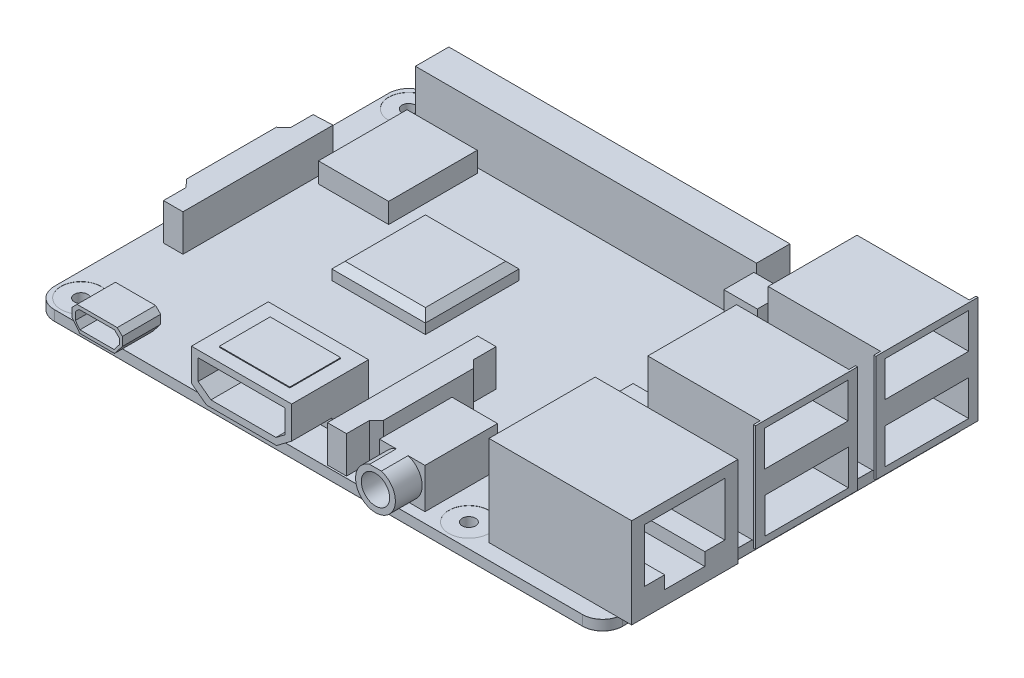
SolidWorks part; units mm, degrees
material "custom glass fiber"
ref_plane "Front Plane" through (0, 0, 0) normal (0, 0, 1) x (1, 0, 0)
ref_plane "Top Plane" through (0, 0, 0) normal (0, 1, 0) x (1, 0, 0)
ref_plane "Right Plane" through (0, 0, 0) normal (1, 0, 0) x (0, 0, -1)
sketch "Sketch1" plane through (0, 0, 0) normal (0, 1, 0) x (1, 0, 0)
  line L0 (32.5, 56) -> (32.5, 0) construction
  line L1 (3, 0) -> (82, 0)
  line L2 (0, 3) -> (0, 53)
  line L3 (3, 56) -> (82, 56)
  line L4 (85, 3) -> (85, 53)
  arc A0 (3, 0) -> (0, 3) centre (3, 3) cw
  arc A1 (82, 0) -> (85, 3) centre (82, 3) ccw
  arc A2 (82, 56) -> (85, 53) centre (82, 53) cw
  arc A3 (0, 53) -> (3, 56) centre (3, 53) cw
  circle A4 centre (3.5, 52.5) radius 1
  circle A5 centre (3.5, 3.5) radius 1
  circle A6 centre (61.5, 3.5) radius 1
  circle A7 centre (61.5, 52.5) radius 1
  point P7 (0, 0)
  point P12 (85, 56)
  point P15 (0, 56)
  dimension "D3" = 3
  dimension "D4" = 2
  dimension "D1" = 56
  dimension "D2" = 85
  dimension "D5" = 49
  dimension "D6" = 3.5
  dimension "D7" = 3.5
  dimension "D8" = 58
extrude "Boss-Extrude1" add sketch "Sketch1" along normal blind 1.4732
sketch "Sketch2" plane through (0, 1.4732, 0) normal (0, 1, 0) x (1, 0, 0)
  line L0 (3, 56) -> (82, 56)
  line L1 (85, 3) -> (85, 53)
  line L2 (85, 3) -> (85, 53) construction
  line L3 (82, 0) -> (3, 0)
  line L4 (0, 3) -> (0, 53)
  line L5 (3.5, 3.5) -> (61.5, 3.5) construction
  line L6 (32.5, 3.5) -> (32.5, 56) construction
  arc A0 (82, 56) -> (85, 53) centre (82, 53) cw
  arc A1 (82, 0) -> (85, 3) centre (82, 3) ccw construction
  arc A2 (85, 3) -> (82, 0) centre (82, 3) cw
  arc A3 (3, 0) -> (0, 3) centre (3, 3) cw
  arc A4 (0, 53) -> (3, 56) centre (3, 53) cw
  circle A5 centre (3.5, 52.5) radius 3
  circle A6 centre (3.5, 3.5) radius 3
  circle A7 centre (61.5, 52.5) radius 3
  circle A8 centre (61.5, 3.5) radius 3
  dimension "D1" = 6
extrude "Boss-Extrude2" add sketch "Sketch2" along normal blind 0.0254 separate body
extrude "Boss-Extrude3" add sketch "Sketch2<2>" against normal blind 0.0254 from surface separate body starting at face at (61.5, 0, -4.5)
sketch "Sketch2<2>" plane through (0, 1.4732, 0) normal (0, 1, 0) x (1, 0, 0) same geometry as "Sketch2"
sketch "Sketch3" plane through (0, 1.4986, 0) normal (0, 1, 0) x (1, 0, 0)
  line L0 (0, 53) -> (0, 3) construction
  line L1 (7, 50) -> (58, 50)
  line L2 (7, 50) -> (7, 55)
  line L3 (7, 55) -> (58, 55)
  line L4 (58, 50) -> (58, 55)
  line L5 (82, 56) -> (3, 56) construction
  line L7 (59, 44.127) -> (64, 44.127)
  line L8 (59, 44.127) -> (59, 48.627)
  line L9 (59, 48.627) -> (64, 48.627)
  line L10 (64, 44.127) -> (64, 48.627)
  line L11 (59, 44.127) -> (64, 48.627) construction
  line L12 (59, 48.627) -> (64, 44.127) construction
  point P8 (61.5, 46.377)
  point P13 (61.5, 52.5)
  dimension "D1" = 58
  dimension "D2" = 6
  dimension "D3" = 51
  dimension "D4" = 5
  dimension "D5" = 9.623
  dimension "D6" = 4.5
  dimension "D7" = 5
extrude "Boss-Extrude4" add sketch "Sketch3" along normal blind 8.5 separate body
sketch "Sketch4" plane through (0, 1.4986, 0) normal (0, 1, 0) x (1, 0, 0)
  line L0 (86.1842, 40.3579) -> (86.1842, 39.3579)
  line L1 (69.39, 40.3579) -> (86.1842, 40.3579)
  line L2 (69.39, 40.3579) -> (69.39, 53.6421)
  line L3 (69.39, 53.6421) -> (86.1842, 53.6421)
  line L4 (85, 3) -> (85, 53) construction
  line L5 (86.4842, 54.6421) -> (86.1842, 54.6421)
  line L6 (86.4842, 54.6421) -> (86.4842, 39.3579)
  line L7 (86.4842, 39.3579) -> (86.1842, 39.3579)
  line L8 (86.1842, 54.6421) -> (86.1842, 53.6421)
  line L10 (3, 0) -> (82, 0) construction
  line L11 (85, 38) -> (69.39, 38) construction
  line L12 (86.1842, 21.3579) -> (86.1842, 22.3579)
  line L13 (86.4842, 36.6421) -> (86.1842, 36.6421)
  line L14 (86.4842, 21.3579) -> (86.4842, 36.6421)
  line L15 (86.4842, 21.3579) -> (86.1842, 21.3579)
  line L16 (69.39, 22.3579) -> (86.1842, 22.3579)
  line L17 (69.39, 35.6421) -> (69.39, 22.3579)
  line L18 (69.39, 35.6421) -> (86.1842, 35.6421)
  line L19 (86.1842, 35.6421) -> (86.1842, 36.6421)
  point P8 (86.4842, 47)
  point P9 (69.39, 47)
  point P16 (69.39, 29)
  point P17 (86.4842, 29)
  dimension "D1" = 15.61
  dimension "D2" = 47
  dimension "D3" = 13.2842
  dimension "D4" = 17.0942
  dimension "D5" = 1
  dimension "D6" = 0.3
  dimension "D7" = 29
extrude "Boss-Extrude5" add sketch "Sketch4" along normal blind 16 separate body
sketch "Sketch5" plane through (0, 1.4986, 0) normal (0, 1, 0) x (1, 0, 0)
  line L0 (3, 0) -> (82, 0) construction
  line L1 (65.6927, 18.1875) -> (87.0287, 18.1875)
  line L2 (65.6927, 18.1875) -> (65.6927, 2.3125)
  line L3 (65.6927, 2.3125) -> (87.0287, 2.3125)
  line L4 (87.0287, 18.1875) -> (87.0287, 2.3125)
  line L5 (85, 3) -> (85, 53) construction
  point P4 (87.0287, 10.25)
  dimension "D1" = 10.25
  dimension "D2" = 21.336
  dimension "D3" = 15.875
  dimension "D4" = 19.3073
extrude "Boss-Extrude6" add sketch "Sketch5" along normal blind 13.5 separate body
sketch "Sketch6" plane through (0, 1.4986, 0) normal (0, 1, 0) x (1, 0, 0)
  line L0 (0, 53) -> (0, 3) construction
  line L1 (24.507, 10.5) -> (39.493, 10.5)
  line L2 (24.507, 10.5) -> (24.507, -0.9935)
  line L3 (24.507, -0.9935) -> (39.493, -0.9935)
  line L4 (39.493, 10.5) -> (39.493, -0.9935)
  line L5 (3, 0) -> (82, 0) construction
  point P4 (32, -0.9935)
  dimension "D1" = 32
  dimension "D2" = 10.5
  dimension "D3" = 14.986
  dimension "D4" = 11.4935
extrude "Boss-Extrude7" add sketch "Sketch6" along normal blind 6.5 separate body
sketch "Sketch7" plane through (0, 1.4986, 0) normal (0, 1, 0) x (1, 0, 0)
  line L0 (5.4688, 39.2259) -> (5.4688, 16.7741)
  line L1 (5.4688, 16.7741) -> (2.5592, 16.7741)
  line L2 (2.5592, 16.7741) -> (2.5592, 20.1357)
  line L3 (2.5592, 20.1357) -> (1.4951, 21.301)
  line L4 (1.4951, 21.301) -> (1.4951, 34.699)
  line L5 (1.4951, 34.699) -> (2.6109, 35.718)
  line L6 (2.6109, 35.718) -> (2.6109, 39.0944)
  line L7 (2.6109, 39.0944) -> (5.4688, 39.2259)
  line L8 (5.4688, 28) -> (1.4951, 28) construction
  line L9 (0, 53) -> (0, 3) construction
  line L11 (3, 0) -> (82, 0) construction
  line L12 (43.5712, 22.7261) -> (43.5712, 0.2739)
  line L13 (43.5712, 0.2739) -> (46.4288, 0.2739)
  line L14 (46.4288, 0.2739) -> (46.4288, 3.7195)
  line L15 (46.4288, 3.7195) -> (47.4644, 4.7551)
  line L16 (47.4644, 4.7551) -> (47.4644, 18.2449)
  line L17 (47.4644, 18.2449) -> (46.3433, 19.366)
  line L18 (46.3433, 19.366) -> (46.3433, 22.7261)
  line L19 (46.3433, 22.7261) -> (43.5712, 22.7261)
  line L20 (47.4644, 11.5) -> (43.5712, 11.5) construction
  line L21 (3, 0) -> (82, 0) construction
  line L22 (24.507, -0.9935) -> (39.493, -0.9935) construction
  point P8 (1.4951, 28)
  point P17 (43.5712, 11.5)
  point P28 (45, 0.2739)
  point P29 (32, -0.9935)
  dimension "D1" = 22.4518
  dimension "D2" = 2.8579
  dimension "D3" = 3.3763
  dimension "D4" = 13.3981
  dimension "D5" = 3.9737
  dimension "D6" = 5.4688
  dimension "D7" = 28
  dimension "D8" = 1.1653
  dimension "D9" = 1.0641
  dimension "D10" = 11.5
  dimension "D11" = 22.4523
  dimension "D12" = 2.7721
  dimension "D13" = 1.1211
  dimension "D14" = 1.1211
  dimension "D15" = 3.3602
  dimension "D16" = 3.4457
  dimension "D17" = 13
extrude "Boss-Extrude8" add sketch "Sketch7" along normal blind 5.5 separate body
sketch "Sketch8" plane through (0, 1.4986, 0) normal (0, 1, 0) x (1, 0, 0)
  line L0 (0, 53) -> (0, 3) construction
  line L1 (50.0964, 12.3762) -> (56.9036, 12.3762)
  line L2 (50.0964, 12.3762) -> (50.0964, -2.4701)
  line L3 (50.0964, -2.4701) -> (56.9036, -2.4701)
  line L4 (56.9036, 12.3762) -> (56.9036, -2.4701)
  line L5 (3, 0) -> (82, 0) construction
  point P4 (53.5, -2.4701)
  dimension "D1" = 6.8072
  dimension "D2" = 14.8463
  dimension "D3" = 53.5
  dimension "D4" = 12.3762
extrude "Boss-Extrude9" add sketch "Sketch8" along normal blind 6 separate body
sketch "Sketch9" plane through (0, 0, 2.4701) normal (0, 0, 1) x (1, 0, 0)
  circle A0 centre (53.5, 4.6546) radius 2.9774
  dimension "D1" = 5.9547
extrude "Cut-Extrude1" cut sketch "Sketch9" against normal blind 4 flip side to cut
sketch "Sketch10" plane through (0, 0, 2.4701) normal (0, 0, 1) x (1, 0, 0)
  circle A0 centre (53.5, 4.6546) radius 2.1197
  dimension "D1" = 4.2395
extrude "Cut-Extrude2" cut sketch "Sketch10" against normal blind 12
sketch "Sketch11" plane through (0, 0, 0.9935) normal (0, 0, 1) x (1, 0, 0)
  line L0 (24.507, 3.1924) -> (26.7613, 1.4986)
  line L1 (24.507, 7.9986) -> (24.507, 1.4986) construction
  line L2 (24.507, 1.4986) -> (39.493, 1.4986) construction
  line L3 (37.2388, 1.4986) -> (39.493, 3.1924)
  line L4 (39.493, 7.9986) -> (39.493, 1.4986) construction
  line L5 (26.7613, 1.4986) -> (24.507, 1.4986)
  line L6 (24.507, 1.4986) -> (24.507, 3.1924)
  line L7 (37.2388, 1.4986) -> (39.493, 1.4986)
  line L8 (39.493, 1.4986) -> (39.493, 3.1924)
  dimension "D1" = 10.4775
  dimension "D2" = 1.6938
extrude "Cut-Extrude3" cut sketch "Sketch11" against normal blind 6
sketch "Sketch12" plane through (0, 7.9986, 0) normal (0, 1, 0) x (1, 0, 0)
  line L0 (32, 4.7533) -> (32, -0.9935) construction
  line L1 (26.7257, 0.9467) -> (37.2743, 0.9467)
  line L2 (26.7257, 0.9467) -> (26.7257, 8.5598)
  line L3 (26.7257, 8.5598) -> (37.2743, 8.5598)
  line L4 (37.2743, 0.9467) -> (37.2743, 8.5598)
  line L5 (26.7257, 0.9467) -> (37.2743, 8.5598) construction
  line L6 (26.7257, 8.5598) -> (37.2743, 0.9467) construction
  line L7 (24.507, -0.9935) -> (39.493, -0.9935) construction
  line L8 (32, -0.9935) -> (24.507, 4.7533) construction
  line L9 (24.507, 10.5) -> (24.507, -0.9935) construction
  line L10 (24.507, 4.7533) -> (32, 4.7533) construction
  line L11 (39.493, 10.5) -> (24.507, 10.5) construction
  point P0 (32, 4.7533)
  dimension "D1" = 1.9402
  dimension "D2" = 10.5485
extrude "Boss-Extrude10" add sketch "Sketch12" along normal blind 0.127 separate body
sketch "Sketch13" plane through (0, 1.4986, 0) normal (0, 1, 0) x (1, 0, 0)
  line L0 (0, 53) -> (0, 3) construction
  line L1 (17, 36) -> (6.5, 36)
  line L2 (17, 36) -> (17, 49.25)
  line L3 (17, 49.25) -> (6.5, 49.25)
  line L4 (6.5, 36) -> (6.5, 49.25)
  line L5 (17, 36) -> (6.5, 49.25) construction
  line L6 (17, 49.25) -> (6.5, 36) construction
  line L7 (82, 56) -> (3, 56) construction
  point P0 (11.75, 42.625)
  dimension "D1" = 10.5
  dimension "D2" = 13.25
  dimension "D3" = 17
  dimension "D4" = 20
extrude "Boss-Extrude11" add sketch "Sketch13" along normal blind 3 separate body
sketch "Sketch14" plane through (0, 1.4986, 0) normal (0, 1, 0) x (1, 0, 0)
  line L0 (0, 53) -> (0, 3) construction
  line L1 (34, 24.5) -> (20, 24.5)
  line L2 (34, 24.5) -> (34, 38.5)
  line L3 (34, 38.5) -> (20, 38.5)
  line L4 (20, 24.5) -> (20, 38.5)
  line L5 (34, 24.5) -> (20, 38.5) construction
  line L6 (34, 38.5) -> (20, 24.5) construction
  line L7 (3, 0) -> (82, 0) construction
  point P0 (27, 31.5)
  dimension "D1" = 14
  dimension "D2" = 14
  dimension "D3" = 27
  dimension "D4" = 31.5
extrude "Boss-Extrude12" add sketch "Sketch14" along normal blind 2.5 separate body
chamfer "Chamfer1" distance 1 angle 45 4 edges at (27, 3.9986, -38.5) (34, 3.9986, -31.5) (27, 3.9986, -24.5) (20, 3.9986, -31.5)
sketch "Sketch15" plane through (0, 1.4986, 0) normal (0, 1, 0) x (1, 0, 0)
  line L0 (0, 53) -> (0, 3) construction
  line L1 (14.3655, 4.5439) -> (6.8344, 4.5439)
  line L2 (14.3655, 4.5439) -> (14.3655, -1.1838)
  line L3 (14.3655, -1.1838) -> (6.8344, -1.1838)
  line L4 (6.8344, 4.5439) -> (6.8344, -1.1838)
  line L5 (14.3655, 4.5439) -> (6.8344, -1.1838) construction
  line L6 (14.3655, -1.1838) -> (6.8344, 4.5439) construction
  line L8 (3, 0) -> (82, 0) construction
  point P0 (10.6, 1.6801)
  dimension "D1" = 10.6
  dimension "D2" = 7.5311
  dimension "D3" = 5.7277
  dimension "D4" = 4.5439
extrude "Boss-Extrude13" add sketch "Sketch15" along normal blind 3.556 separate body
sketch "Sketch16" plane through (0, 0, 1.1838) normal (0, 0, 1) x (1, 0, 0)
  line L0 (8.0036, 1.4986) -> (6.8344, 2.9843)
  line L1 (6.8344, 1.4986) -> (14.3655, 1.4986) construction
  line L2 (6.8344, 5.0546) -> (6.8344, 1.4986) construction
  line L3 (6.8344, 2.9843) -> (6.8344, 4.2921)
  line L4 (6.8344, 4.2921) -> (7.5969, 5.0546)
  line L5 (6.8344, 5.0546) -> (14.3655, 5.0546) construction
  line L6 (7.5969, 5.0546) -> (13.6031, 5.0546)
  line L7 (10.6, 5.0546) -> (10.6, 1.4986) construction
  line L8 (13.1964, 1.4986) -> (8.0036, 1.4986)
  line L9 (14.3655, 4.2921) -> (13.6031, 5.0546)
  line L10 (14.3655, 2.9843) -> (14.3655, 4.2921)
  line L11 (13.1964, 1.4986) -> (14.3655, 2.9843)
  dimension "D1" = 1.3078
  dimension "D2" = 3.0031
  dimension "D3" = 1.4857
  dimension "D4" = 1.1692
extrude "Cut-Extrude4" cut sketch "Sketch16" against normal through all flip side to cut
sketch "Sketch20" plane through (0, 1.4986, 0) normal (0, 1, 0) x (1, 0, 0)
  line L0 (3, 0) -> (82, 0) construction
  line L1 (56.86, 23.6901) -> (65.86, 23.6901)
  line L2 (56.86, 23.6901) -> (56.86, 32.6901)
  line L3 (56.86, 32.6901) -> (65.86, 32.6901)
  line L4 (65.86, 23.6901) -> (65.86, 32.6901)
  line L5 (56.86, 23.6901) -> (65.86, 32.6901) construction
  line L6 (56.86, 32.6901) -> (65.86, 23.6901) construction
  line L7 (85, 3) -> (85, 53) construction
  line L8 (0, 53) -> (0, 3) construction
  point P0 (61.36, 28.1901)
  dimension "D1" = 9
  dimension "D2" = 9
  dimension "D3" = 28.1901
  dimension "D4" = 23.64
  dimension "D16" = 82
  dimension "D23" = 53
  dimension "D24" = 82
  dimension "D27" = 53
  dimension "D29" = 82
  dimension "D34" = 82
  dimension "D37" = 53
extrude "Boss-Extrude15" add sketch "Sketch20" along normal blind 1 separate body
sketch "Sketch23" plane through (86.4842, 0, 0) normal (1, 0, 0) x (0, 0, -1)
  line L0 (40.75, 16.4986) -> (40.75, 11.1986)
  line L1 (40.75, 11.1986) -> (53.25, 11.1986)
  line L2 (53.25, 11.1986) -> (53.25, 16.4986)
  line L3 (53.25, 16.4986) -> (40.75, 16.4986)
  line L4 (40.75, 7.7986) -> (40.75, 2.4986)
  line L5 (40.75, 2.4986) -> (53.25, 2.4986)
  line L6 (53.25, 2.4986) -> (53.25, 7.7986)
  line L7 (53.25, 7.7986) -> (40.75, 7.7986)
  line L8 (47, 16.4986) -> (47, 11.1986) construction
  line L9 (47, 7.7986) -> (47, 2.4986) construction
  line L14 (39.3579, 17.4986) -> (54.6421, 17.4986) construction
  line L15 (39.3579, 1.4986) -> (54.6421, 1.4986) construction
  dimension "D1" = 12.5
  dimension "D2" = 5.3
  dimension "D3" = 1
  dimension "D4" = 1
sketch "Sketch26" plane through (86.4842, 0, 0) normal (1, 0, 0) x (0, 0, -1)
  line L1 (22.718, 16.4986) -> (35.218, 16.4986)
  line L2 (22.718, 16.4986) -> (22.718, 11.1986)
  line L3 (22.718, 11.1986) -> (35.218, 11.1986)
  line L4 (35.218, 16.4986) -> (35.218, 11.1986)
  line L5 (22.718, 16.4986) -> (35.218, 11.1986) construction
  line L6 (22.718, 11.1986) -> (35.218, 16.4986) construction
  line L7 (22.782, 7.7986) -> (35.282, 7.7986)
  line L8 (22.782, 7.7986) -> (22.782, 2.4986)
  line L9 (22.782, 2.4986) -> (35.282, 2.4986)
  line L10 (35.282, 7.7986) -> (35.282, 2.4986)
  line L11 (22.782, 7.7986) -> (35.282, 2.4986) construction
  line L12 (22.782, 2.4986) -> (35.282, 7.7986) construction
  line L13 (21.3579, 1.4986) -> (36.6421, 1.4986) construction
  line L14 (21.3579, 17.4986) -> (36.6421, 17.4986) construction
  point P0 (28.968, 13.8486)
  point P5 (29.032, 5.1486)
  dimension "D1" = 12.5
  dimension "D2" = 5.3
  dimension "D3" = 5.3
  dimension "D4" = 12.5
  dimension "D5" = 1
  dimension "D6" = 1
extrude "Cut-Extrude6" cut sketch "Sketch23" against normal blind 13
extrude "Cut-Extrude7" cut sketch "Sketch26" against normal blind 13
sketch "Sketch27" plane through (87.0287, 0, 0) normal (1, 0, 0) x (0, 0, -1)
  line L0 (4.25, 13.5332) -> (16.25, 13.5332)
  line L1 (16.25, 13.5332) -> (16.25, 5.5332)
  line L2 (16.25, 5.5332) -> (4.25, 5.5332)
  line L3 (4.25, 5.5332) -> (4.25, 13.5332)
  line L5 (2.3125, 14.9986) -> (18.1875, 14.9986) construction
  line L6 (7.25, 5.5332) -> (7.25, 3.6112)
  line L7 (7.25, 3.6112) -> (13.25, 3.6112)
  line L8 (13.25, 3.6112) -> (13.25, 5.5332)
  point P2 (10.25, 13.5332)
  point P7 (10.25, 14.9986)
  dimension "D1" = 12
  dimension "D2" = 8
  dimension "D3" = 3
  dimension "D4" = 3
extrude "Cut-Extrude8" cut sketch "Sketch27" against normal blind 13 contours L3 L2 L1 L0 | L7 L8 L2 L6 region at (87.0287, 9.5332, -10.25) region at (87.0287, 4.5722, -10.25)
sketch "Sketch29" plane through (0, 0, 0.9935) normal (0, 0, 1) x (1, 0, 0)
  line L0 (25.507, 6.9986) -> (38.493, 6.9986)
  line L1 (38.493, 6.9986) -> (38.493, 3.5157)
  line L2 (38.493, 3.5157) -> (37.1394, 2.4986)
  line L3 (37.1394, 2.4986) -> (27.4193, 2.4986)
  line L4 (27.4193, 2.4986) -> (25.507, 3.9354)
  line L5 (25.507, 3.9354) -> (25.507, 6.9986)
  line L6 (26.7613, 1.4986) -> (24.507, 3.1924) construction
  line L7 (39.493, 3.1924) -> (37.2388, 1.4986) construction
  line L8 (24.507, 7.9986) -> (24.507, 3.1924) construction
  line L10 (26.7257, 7.9986) -> (37.2743, 7.9986) construction
  line L11 (39.493, 7.9986) -> (39.493, 3.1924) construction
  line L12 (26.7613, 1.4986) -> (37.2388, 1.4986) construction
  dimension "D1" = 1
  dimension "D2" = 1
  dimension "D3" = 1
  dimension "D4" = 1
extrude "Cut-Extrude9" cut sketch "Sketch29" against normal blind 10
sketch "Sketch30" plane through (0, 0, 1.1838) normal (0, 0, 1) x (1, 0, 0)
  line L0 (7.3417, 2.8424) -> (7.3417, 4.0032)
  line L1 (7.3417, 4.0032) -> (7.8931, 4.5546)
  line L2 (7.8931, 4.5546) -> (13.2038, 4.5546)
  line L3 (13.2038, 4.5546) -> (13.9248, 3.8336)
  line L4 (13.9248, 3.8336) -> (13.9248, 2.993)
  line L5 (13.9248, 2.993) -> (13.1223, 1.9732)
  line L6 (13.1223, 1.9732) -> (8.0257, 1.9732)
  line L7 (8.0257, 1.9732) -> (7.3417, 2.8424)
  line L8 (6.8344, 2.9843) -> (8.0036, 1.4986) construction
  line L9 (13.1964, 1.4986) -> (14.3655, 2.9843) construction
  line L14 (7.5969, 5.0546) -> (6.8344, 4.2921) construction
  line L15 (14.3655, 4.2921) -> (13.6031, 5.0546) construction
  line L16 (7.5969, 5.0546) -> (13.6031, 5.0546) construction
  line L17 (3, 1.4732) -> (82, 1.4732) construction
  dimension "D1" = 0.5
  dimension "D2" = 0.5
extrude "Cut-Extrude10" cut sketch "Sketch30" against normal blind 4
